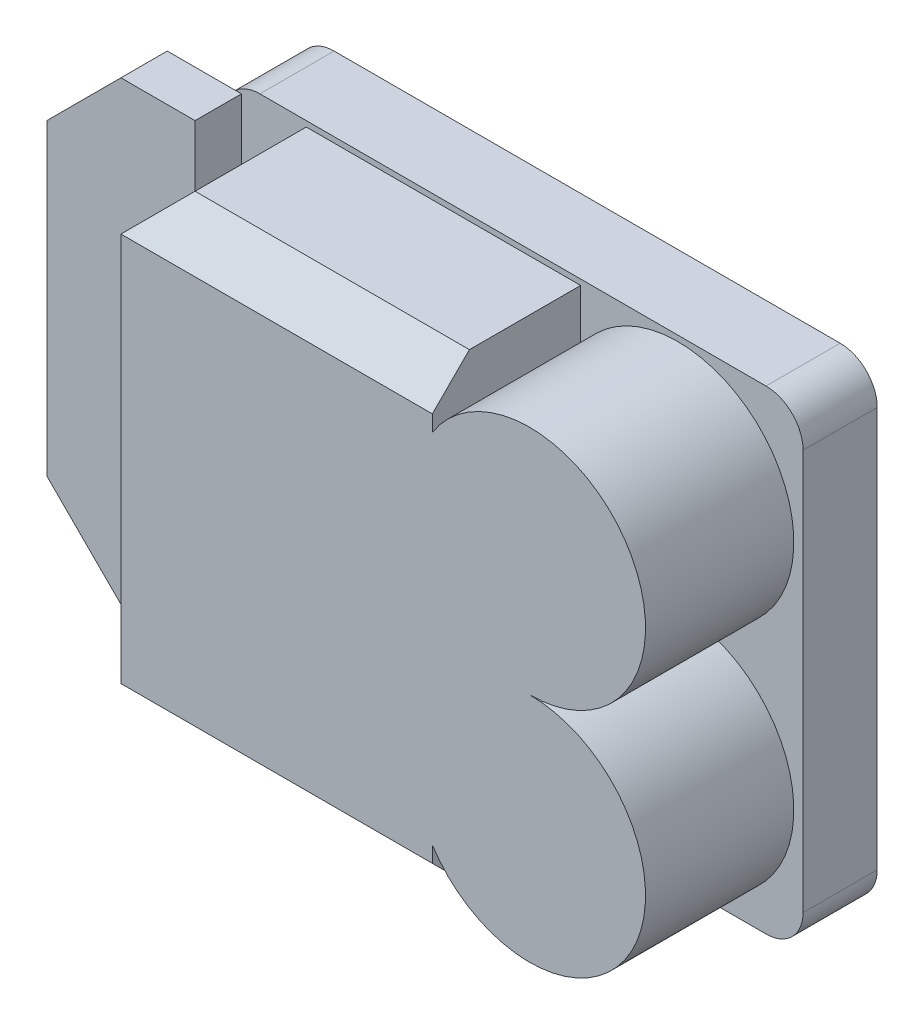
SolidWorks part; units mm, degrees
material "PEI"
ref_plane "前视基准面" through (0, 0, 0) normal (0, 0, 1) x (1, 0, 0)
ref_plane "上视基准面" through (0, 0, 0) normal (0, 1, 0) x (1, 0, 0)
ref_plane "右视基准面" through (0, 0, 0) normal (1, 0, 0) x (0, 0, -1)
other "Configuration Table"
sketch "草图1" plane through (0, 0, 0) normal (0, 0, 1) x (1, 0, 0)
  line L0 (22.05, 12.5) -> (29.8479, 12.5) construction
  line L1 (0, 0) -> (28.3, 0)
  line L2 (0, 0) -> (0, 25)
  line L3 (0, 25) -> (28.3, 25)
  line L4 (28.3, 0) -> (28.3, 25)
  line L5 (0, 25) -> (15.8, 25)
  line L6 (0, 25) -> (0, 0)
  line L7 (0, 0) -> (15.8, 0)
  line L8 (15.8, 25) -> (15.8, 0)
  line L9 (15.8, 25) -> (16.8, 25)
  line L10 (15.8, 25) -> (15.8, 0)
  line L11 (15.8, 0) -> (16.8, 0)
  line L12 (16.8, 25) -> (16.8, 0)
  line L13 (28.3, 11.5) -> (15.8, 11.5)
  line L14 (28.3, 11.5) -> (28.3, 13.5)
  line L15 (28.3, 13.5) -> (15.8, 13.5)
  line L16 (15.8, 11.5) -> (15.8, 13.5)
  circle A0 centre (22.05, 18.75) radius 6.25
  circle A1 centre (22.05, 6.25) radius 6.25
  dimension "D1" = 25
  dimension "D2" = 28.3
  dimension "D3" = 2
  dimension "D4" = 1
extrude "凸台-拉伸1" add sketch "草图1" along normal blind 8 contours L8 L3 L2 L1 L10 | A0 L12 L3 L8 | L12 A0 | A0 L10 L15 L12 | L12 A0 L15 | L13 A1 L12 | A1 A0 L15 L12 L13 | A0 L12 L15 | L12 L15 L10 L13 | L12 A1 | A1 L12 L13 L10 | A1 L8 L1 L12 | L13 A1 | L15 A0 | A1 L13 L12 region at (7.9, 12.5, 0) region at (16.2435, 2.0547, 0) region at (16.2243, 9.9183, 0) region at (16.3971, 6.25, 0) region at (16.2435, 22.9453, 0) region at (22.279, 6.021, 0) region at (16.3, 12.5, 0) region at (17.3748, 10.9252, 0) region at (16.2243, 15.0817, 0) region at (16.3971, 18.75, 0) region at (18.3817, 12.5, 0) region at (22.05, 11.9029, 0) region at (22.279, 18.979, 0) region at (17.3748, 14.0748, 0) region at (22.05, 13.0971, 0)
sketch "草图2" plane through (0, 0, 0) normal (0, 0, -1) x (-1, 0, 0)
  line L0 (0, 25) -> (-16.8, 25) construction
  line L1 (2.5, 25.3) -> (-28.8, 25.3)
  line L2 (2.5, 25.3) -> (2.5, -0.3)
  line L3 (2.5, -0.3) -> (-28.8, -0.3)
  line L4 (-28.8, 25.3) -> (-28.8, -0.3)
  line L5 (0, 0) -> (-16.8, 0) construction
  line L6 (0, 0) -> (0, 25) construction
  line L8 (-16.8, 25) -> (-16.8, 22.1412) construction
  dimension "D1" = 0.3
  dimension "D2" = 12
  dimension "D3" = 0.3
  dimension "D4" = 2.5
extrude "凸台-拉伸12" add sketch "草图2" along normal blind 4
sketch "草图3" plane through (-2.5, 0, 0) normal (-1, 0, 0) x (0, 0, 1)
  line L0 (-4, 25.3) -> (0, 25.3) construction
  line L1 (0, 24.8) -> (2.5, 24.8)
  line L2 (0, 24.8) -> (0, 0.2)
  line L3 (0, 0.2) -> (2.5, 0.2)
  line L4 (2.5, 24.8) -> (2.5, 0.2)
  line L5 (-4, -0.3) -> (0, -0.3) construction
  line L6 (0, 0) -> (0, 25) construction
  dimension "D1" = 0.5
  dimension "D2" = 0.5
  dimension "D3" = 2.5
extrude "凸台-拉伸13" add sketch "草图3" along normal blind 7 and the other way blind 1
chamfer "倒角1" distance 4 angle 45 2 edges at (-9.5, 0.2, 1.25) (-9.5, 24.8, 1.25)
fillet "圆角1" radius 2 4 edges at (28.8, 25.3, -2) (28.8, -0.3, -2) (-2.5, -0.3, -2) (-2.5, 25.3, -2)
chamfer "倒角2" distance 2 angle 45 4 edges at (8.4, 0, 8) (0, 0, 4) (8.4, 25, 8) (0, 25, 4)
